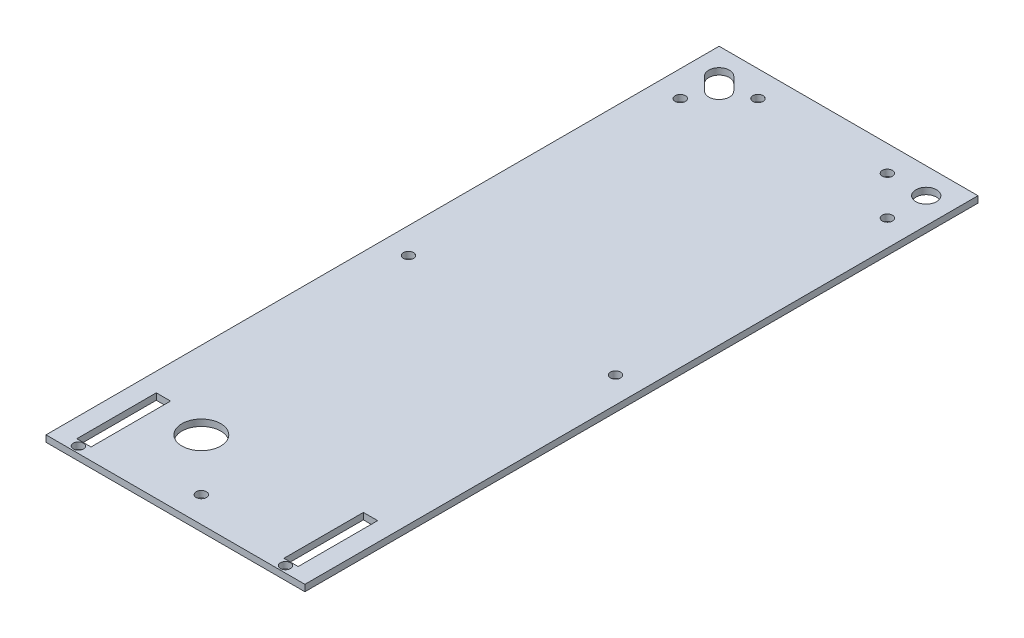
SolidWorks part; units mm, degrees
ref_plane "Front Plane" through (0, 0, 0) normal (0, 0, 1) x (1, 0, 0)
ref_plane "Top Plane" through (0, 0, 0) normal (0, 1, 0) x (1, 0, 0)
ref_plane "Right Plane" through (0, 0, 0) normal (1, 0, 0) x (0, 0, -1)
sketch "Sketch1" plane through (0, 0, 0) normal (0, 1, 0) x (1, 0, 0)
  line L1 (63.5, -165.1) -> (-63.5, -165.1)
  line L2 (63.5, -165.1) -> (63.5, 165.1)
  line L3 (63.5, 165.1) -> (-63.5, 165.1)
  line L4 (-63.5, -165.1) -> (-63.5, 165.1)
  line L5 (63.5, -165.1) -> (-63.5, 165.1) construction
  line L6 (63.5, 165.1) -> (-63.5, -165.1) construction
  point P0 (0, 0)
  dimension "D1" = 330.2
  dimension "D2" = 127
extrude "Boss-Extrude1" add sketch "Sketch1" along normal blind 3.175
sketch "Sketch2" plane through (0, 3.175, 0) normal (0, 1, 0) x (1, 0, 0)
  line L0 (-63.5, 165.1) -> (-63.5, -165.1) construction
  line L1 (63.5, 165.1) -> (-63.5, 165.1) construction
  line L2 (0, 165.1) -> (0, 0) construction
  line L3 (0, 0) -> (-63.5, 0) construction
  line L4 (-63.5, -165.1) -> (63.5, -165.1) construction
  line L8 (-54.3921, 148.8079) -> (-48.0421, 142.4579)
  line L9 (-47.2079, 155.9921) -> (-40.8579, 149.6421)
  circle A0 centre (-50.8, 152.4) radius 2.5
  circle A1 centre (-44.45, 146.05) radius 2.5
  circle A3 centre (50.8, 152.4) radius 2.5
  circle A6 centre (50.8, 152.4) radius 2.5
  arc A36 (-48.0421, 142.4579) -> (-40.8579, 149.6421) centre (-44.45, 146.05) ccw
  arc A37 (-47.2079, 155.9921) -> (-54.3921, 148.8079) centre (-50.8, 152.4) ccw
  circle A38 centre (50.8, 152.4) radius 5.08
  circle A39 centre (-31.75, 152.4) radius 2.5
  circle A40 centre (31.75, 152.4) radius 2.5
  circle A41 centre (-50.8, 133.35) radius 2.5
  circle A42 centre (50.8, 133.35) radius 2.5
  circle A47 centre (-50.8, -161.925) radius 2.5
  circle A48 centre (50.8, -161.925) radius 2.5
  circle A51 centre (-50.8, 0) radius 2.5
  circle A53 centre (50.8, 0) radius 2.5
  circle A54 centre (0, -152.4) radius 2.5
  circle A55 centre (-12.7, 152.4) radius 2.05
  circle A56 centre (25.4, 152.4) radius 2.05
  circle A57 centre (-12.7, 164.85) radius 3.175
  circle A58 centre (25.4, 164.85) radius 3.175
  point P44 (0, 0)
  point P47 (0, 0)
  dimension "D1" = 5
  dimension "D15" = 10.16
  dimension "D6" = 31.75
  dimension "D13" = 4.1
  dimension "D18" = 6.35
  dimension "D2" = 12.7
  dimension "D3" = 12.7
  dimension "D4" = 19.05
  dimension "D5" = 19.05
  dimension "D7" = 12.7
  dimension "D8" = 12.7
  dimension "D9" = 31.75
  dimension "D10" = 12.7
  dimension "D11" = 3.175
  dimension "D14" = 38.1
  dimension "D12" = 12.7
  dimension "D16" = 38.1
  dimension "D17" = 12.45
extrude "Cut-Extrude1" cut sketch "Sketch2" against normal blind 25.4 contours A3 | A0 | A1 | L9 A37 L8 A36 A1 A0 | A38 A3 | A39 | A40 | A41 | A42 | A47 | A48 | A51 | A53 | A54
sketch "Sketch3" plane through (0, 3.175, 0) normal (0, 1, 0) x (1, 0, 0)
  line L0 (-63.5, -165.1) -> (63.5, -165.1) construction
  line L1 (63.5, -139.7) -> (-63.5, -139.7) construction
  line L2 (-63.5, 165.1) -> (-63.5, -165.1) construction
  line L3 (63.5, -165.1) -> (63.5, 165.1) construction
  line L4 (63.5, 165.1) -> (-63.5, 165.1) construction
  line L5 (-54.3, -159.2) -> (-47.3, -152.2) construction
  line L6 (-54.3, -127.2) -> (-47.3, -127.2) construction
  line L7 (-54.3, -127.2) -> (-54.3, -120.2)
  line L8 (-54.3, -120.2) -> (-47.3, -120.2)
  line L9 (-47.3, -127.2) -> (-47.3, -120.2)
  line L10 (-54.3, -127.2) -> (-47.3, -120.2) construction
  line L11 (-54.3, -120.2) -> (-47.3, -127.2) construction
  line L12 (-54.3, -152.2) -> (-47.3, -159.2) construction
  line L13 (-47.3, -152.2) -> (-47.3, -159.2)
  line L14 (-54.3, -159.2) -> (-47.3, -159.2)
  line L15 (-54.3, -152.2) -> (-54.3, -159.2)
  line L16 (-54.3, -152.2) -> (-47.3, -152.2) construction
  line L17 (-47.3, -152.2) -> (-47.3, -127.2)
  line L18 (-54.3, -120.2) -> (-47.3, -120.2)
  line L20 (-54.3, -159.2) -> (-47.3, -159.2)
  line L22 (-54.3, -127.2) -> (-54.3, -152.2)
  line L23 (0, -139.7) -> (0, -165.1) construction
  line L24 (54.3, -152.2) -> (47.3, -152.2) construction
  line L25 (54.3, -152.2) -> (47.3, -159.2) construction
  line L26 (54.3, -120.2) -> (47.3, -127.2) construction
  line L27 (54.3, -127.2) -> (47.3, -120.2) construction
  line L28 (54.3, -127.2) -> (47.3, -127.2) construction
  line L29 (54.3, -159.2) -> (47.3, -152.2) construction
  line L30 (54.3, -127.2) -> (54.3, -152.2)
  line L31 (54.3, -159.2) -> (47.3, -159.2)
  line L32 (54.3, -120.2) -> (47.3, -120.2)
  line L33 (47.3, -152.2) -> (47.3, -127.2)
  line L34 (54.3, -152.2) -> (54.3, -159.2)
  line L35 (54.3, -159.2) -> (47.3, -159.2)
  line L36 (47.3, -152.2) -> (47.3, -159.2)
  line L37 (47.3, -127.2) -> (47.3, -120.2)
  line L38 (54.3, -120.2) -> (47.3, -120.2)
  line L39 (54.3, -127.2) -> (54.3, -120.2)
  circle A0 centre (-25.4, -127) radius 9.525
  point P12 (-50.8, -123.7)
  point P21 (-50.8, -155.7)
  point P32 (50.8, -155.7)
  point P33 (50.8, -123.7)
  circle M17 centre (-50.8, -161.925) radius 2.5
  dimension "D1" = 19.05
  dimension "D2" = 38.1
  dimension "D3" = 38.1
  dimension "D4" = 304.8
  dimension "D5" = 7
  dimension "D6" = 16
  dimension "D7" = 12.7
extrude "Cut-Extrude2" cut sketch "Sketch3" against normal blind 25.4 contours L7 L22 L15 L14 L13 L17 L9 L8 M17 | A0 | L30 L39 L32 L37 L33 L36 L31 L34 region at (-50.8, 3.175, 139.7) region at (50.8, 3.175, 139.7) region at (-25.4, 3.175, 127)
